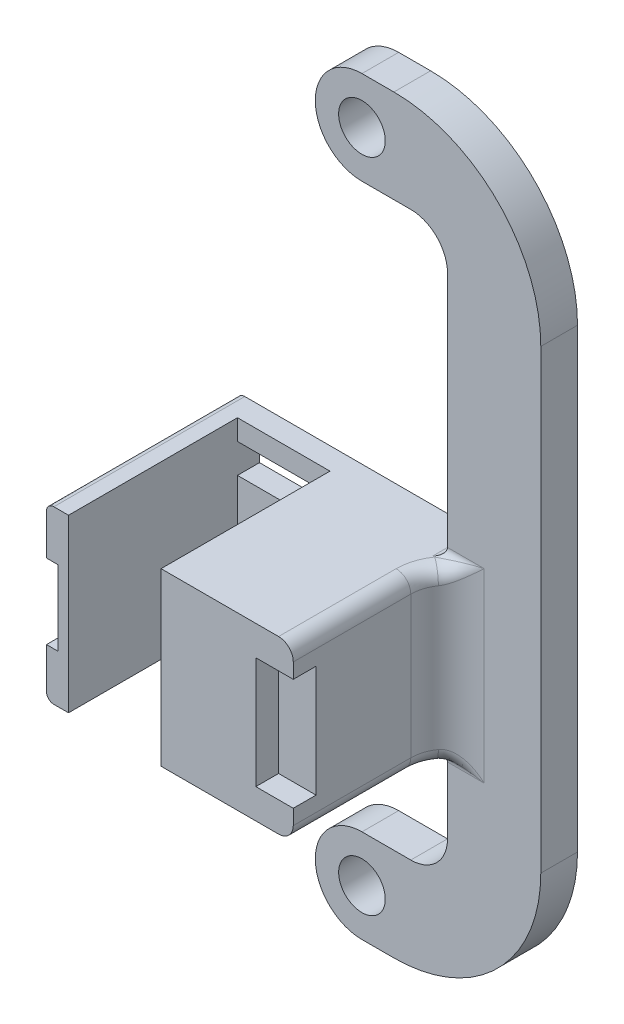
SolidWorks part; units mm, degrees
ref_plane "Front Plane" through (0, 0, 0) normal (0, 0, 1) x (1, 0, 0)
ref_plane "Top Plane" through (0, 0, 0) normal (0, 1, 0) x (1, 0, 0)
ref_plane "Right Plane" through (0, 0, 0) normal (1, 0, 0) x (0, 0, -1)
sketch "Sketch1" plane through (0, 0, 0) normal (0, 1, 0) x (1, 0, 0)
  line L1 (-6.3, -11.5) -> (6.3, -11.5)
  line L2 (-6.3, -11.5) -> (-6.3, 11.5)
  line L3 (-6.3, 11.5) -> (6.3, 11.5)
  line L4 (6.3, -11.5) -> (6.3, 11.5)
  line L5 (-6.3, -11.5) -> (6.3, 11.5) construction
  line L6 (-6.3, 11.5) -> (6.3, -11.5) construction
  point P0 (0, 0)
  dimension "D1" = 23
  dimension "D2" = 12.6
extrude "Extrude-Thin1" add sketch "Sketch1" along normal blind 23.3 thin thin type one direction wall 3
sketch "Sketch2" plane through (0, 0, 14.5) normal (0, 0, 1) x (1, 0, 0)
  line L0 (0, 23.3) -> (0, 0) construction
  line L1 (-9.3, 23.3) -> (9.3, 23.3) construction
  line L2 (-9.3, 0) -> (9.3, 0) construction
  line L4 (-6.3, 16.5) -> (6.3, 16.5)
  line L5 (-6.3, 16.5) -> (-6.3, 20.5)
  line L6 (-6.3, 20.5) -> (6.3, 20.5)
  line L7 (6.3, 16.5) -> (6.3, 20.5)
  line L8 (-6.3, 16.5) -> (6.3, 20.5) construction
  line L9 (-6.3, 20.5) -> (6.3, 16.5) construction
  point P6 (0, 18.5)
  dimension "D1" = 16.5
  dimension "D2" = 4
  dimension "D3" = 12.6
extrude "Cut-Extrude1" cut sketch "Sketch2" against normal through all
sketch "Sketch5" plane through (9.3, 0, 0) normal (1, 0, 0) x (0, 0, -1)
  line L1 (-14.5, 23.3) -> (14.5, 23.3)
  line L2 (-14.5, 23.3) -> (-14.5, 0)
  line L3 (-14.5, 0) -> (14.5, 0)
  line L4 (14.5, 23.3) -> (14.5, 0)
extrude "Boss-Extrude2" add sketch "Sketch5" along normal blind 15
sketch "Sketch6" plane through (0, 0, -14.5) normal (0, 0, -1) x (-1, 0, 0)
  line L0 (-24.3, 23.3) -> (9.3, 23.3) construction
  line L1 (-24.3, 68.004) -> (-37, 68.004)
  line L2 (-24.3, 68.004) -> (-24.3, -21.404)
  line L3 (-24.3, -21.404) -> (-37, -21.404)
  line L4 (-37, 68.004) -> (-37, -21.404)
  line L5 (-24.3, 0) -> (-24.3, 23.3) construction
  line L6 (-30.65, 68.004) -> (-12.65, 68.004)
  line L7 (-30.65, -15.054) -> (-12.65, -15.054)
  line L8 (-30.65, 71.179) -> (-12.65, 71.179)
  line L9 (-30.65, 71.179) -> (-30.65, 64.829)
  line L10 (-30.65, 64.829) -> (-12.65, 64.829)
  line L11 (-12.65, 71.179) -> (-12.65, 64.829)
  line L12 (-30.65, 74.354) -> (-12.65, 74.354)
  line L13 (-30.65, 74.354) -> (-30.65, 61.654)
  line L14 (-30.65, 61.654) -> (-12.65, 61.654)
  line L15 (-12.65, 74.354) -> (-12.65, 61.654)
  line L16 (-30.65, -27.754) -> (-12.65, -27.754)
  line L17 (-30.65, -27.754) -> (-37, -27.754)
  line L18 (-30.65, 61.654) -> (-37, 61.654)
  line L19 (-30.65, 61.654) -> (-30.65, 74.354)
  line L20 (-30.65, 74.354) -> (-37, 74.354)
  line L21 (-37, 61.654) -> (-37, 74.354)
  line L22 (-37, -15.054) -> (-37, -27.754)
  line L23 (-30.65, -15.054) -> (-37, -15.054)
  line L24 (-30.65, -15.054) -> (-30.65, -27.754)
  circle A0 centre (-30.65, 68.004) radius 3.175
  circle A1 centre (-30.65, -21.404) radius 3.175
  circle A2 centre (-30.65, 68.004) radius 6.35
  circle A3 centre (-30.65, -21.404) radius 6.35
  circle A4 centre (-12.65, 68.004) radius 3.175
  circle A5 centre (-12.65, 68.004) radius 6.35
  circle A6 centre (-12.65, -21.404) radius 3.175
  circle A7 centre (-12.65, -21.404) radius 6.35
  line M8 (-24.3, 23.3) -> (-24.3, 0)
  dimension "D3" = 6.35
  dimension "D4" = 6.35
  dimension "D5" = 12.7
  dimension "D1" = 89.408
  dimension "D2" = 44.704
  dimension "D6" = 0
  dimension "D7" = 18
extrude "Boss-Extrude3" add sketch "Sketch6" against normal blind 5 contours L23 L7 L2 L14 L18 L4 M8 | A2 L20 L21 | A2 L4 L18 | A2 L14 L2 L10 | A2 L10 L2 | A5 L8 A2 L6 | A5 L12 A2 L8 | A5 L6 L2 L10 | A5 L10 L2 L14 | L6 A5 L10 A4 | L8 A5 L6 A4 | L15 A5 L8 | L10 A5 L15 | L15 A5 A4 | A3 L23 L4 | L24 A3 L3 A1 | L3 A3 L24 A1 | A3 L2 L7 | L24 A3 L3 A1 | L3 A3 L24 A1 | A3 L22 L17 | L16 A7 L7 L2 A3 | A7 A6 | L3 A1 L24 | L24 A1 L3 | L3 A1 L24 | L24 A1 L3 | A2 region at (21.5066, 66.3767, -14.5) region at (21.65, 69.6673, -14.5) region at (24.552, 65.6117, -14.5) region at (20.3224, 63.0978, -14.5) region at (25.8496, 62.7868, -14.5) region at (16.8727, 69.6967, -14.5) region at (16.8727, 66.3113, -14.5) region at (21.65, 72.9849, -14.5) region at (30.65, 23.3, -14.5) region at (14.8039, 63.5271, -14.5) region at (14.8039, 72.4809, -14.5) region at (35.5816, 72.9356, -14.5) region at (35.5816, 63.0724, -14.5) region at (12.508, 63.2415, -14.5) region at (35.5816, -16.4724, -14.5) region at (21.2725, -21.8615, -14.5) region at (25.7184, -16.4724, -14.5) region at (33.7942, -18.2598, -14.5) region at (35.5816, -26.3356, -14.5) region at (33.7942, -24.5482, -14.5) region at (27.5058, -18.2598, -14.5) region at (27.5058, -24.5482, -14.5) region at (8.2869, -17.0409, -14.5) region at (31.9975, -20.0565, -14.5) region at (31.9975, -22.7515, -14.5) region at (29.3025, -20.0565, -14.5) region at (29.3025, -22.7515, -14.5)
fillet "Fillet1" radius 1 2 edges at (-9.3, 23.3, 0) (-9.3, 0, 0)
fillet "Fillet3" radius 5 1 edges at (24.3, 11.65, -9.5)
fillet "Fillet4" radius 1 4 edges at (24.3, 0, -12) (26.8, 0, -9.5) (26.8, 23.3, -9.5) (24.3, 23.3, -12)
fillet "Fillet5" radius 2 6 edges at (27.0916, 23.426, -8.9859) (24.8279, 23.3, -6.7361) (27.0916, -0.126, -8.9859) (24.8279, 0, -6.7361) (24.3, 23.3, 5) (24.3, 0, 5)
fillet "Fillet6" radius 5 2 edges at (24.3, -15.054, -12) (24.3, 61.654, -12)
fillet "Fillet7" radius 20 2 edges at (37, 74.354, -12) (37, -27.754, -12)
sketch "Sketch7" plane through (0, 0, 14.5) normal (0, 0, 1) x (1, 0, 0)
  line L0 (-9.3, 11.65) -> (24.3, 11.65) construction
  line L2 (-4.8, 6.65) -> (-7.8, 6.65)
  line L3 (-4.8, 6.65) -> (-4.8, 16.65)
  line L4 (6.3, 16.5) -> (-6.3, 16.5)
  line L5 (6.3, 0) -> (6.3, 16.5)
  line L6 (-6.3, 0) -> (6.3, 0)
  line L7 (-6.3, 16.5) -> (-6.3, 0)
  line L8 (6.3, 16.5) -> (-6.3, 16.5)
  line L9 (6.3, 0) -> (6.3, 16.5)
  line L10 (-6.3, 0) -> (6.3, 0)
  line L11 (-6.3, 16.5) -> (-6.3, 0)
  line L12 (-6.3, 20.5) -> (6.3, 20.5)
  line L13 (-6.3, 23.3) -> (-6.3, 20.5)
  line L14 (6.3, 23.3) -> (-6.3, 23.3)
  line L15 (6.3, 20.5) -> (6.3, 23.3)
  line L16 (-6.3, 20.5) -> (6.3, 20.5)
  line L17 (-6.3, 23.3) -> (-6.3, 20.5)
  line L18 (6.3, 23.3) -> (-6.3, 23.3)
  line L19 (6.3, 20.5) -> (6.3, 23.3)
  line L20 (24.3, 2) -> (24.3, 21.3)
  line L21 (22.3, 23.3) -> (-8.3, 23.3)
  line L22 (-9.3, 22.3) -> (-9.3, 1)
  line L23 (-8.3, 0) -> (22.3, 0)
  line L24 (24.3, 2) -> (24.3, 21.3)
  line L25 (22.3, 23.3) -> (-8.3, 23.3)
  line L26 (-9.3, 22.3) -> (-9.3, 1)
  line L27 (-8.3, 0) -> (22.3, 0)
  line L28 (-4.8, 16.65) -> (-7.8, 16.65)
  line L29 (-7.8, 6.65) -> (-7.8, 16.65)
  line L30 (-4.8, 6.65) -> (-7.8, 16.65) construction
  line L31 (-4.8, 16.65) -> (-7.8, 6.65) construction
  line L32 (19.3, 4.15) -> (29.3, 4.15)
  line L33 (19.3, 4.15) -> (19.3, 19.15)
  line L34 (19.3, 19.15) -> (29.3, 19.15)
  line L35 (29.3, 4.15) -> (29.3, 19.15)
  line L36 (19.3, 4.15) -> (29.3, 19.15) construction
  line L37 (19.3, 19.15) -> (29.3, 4.15) construction
  arc A4 (24.3, 21.3) -> (22.3, 23.3) centre (22.3, 21.3) ccw
  arc A5 (-8.3, 23.3) -> (-9.3, 22.3) centre (-8.3, 22.3) ccw
  arc A6 (-9.3, 1) -> (-8.3, 0) centre (-8.3, 1) ccw
  arc A7 (22.3, 0) -> (24.3, 2) centre (22.3, 2) ccw
  arc A8 (24.3, 21.3) -> (22.3, 23.3) centre (22.3, 21.3) ccw
  arc A9 (-8.3, 23.3) -> (-9.3, 22.3) centre (-8.3, 22.3) ccw
  arc A10 (-9.3, 1) -> (-8.3, 0) centre (-8.3, 1) ccw
  arc A11 (22.3, 0) -> (24.3, 2) centre (22.3, 2) ccw
  point P20 (-6.3, 11.65)
  point P21 (-6.3, 11.65)
  dimension "D4" = 10
  dimension "D5" = 3
  dimension "D6" = 10
  dimension "D7" = 15
  dimension "D1" = 0
  dimension "D2" = 0
  dimension "D3" = 0
sketch "Sketch8" plane through (-9.3, 0, 0) normal (-1, 0, 0) x (0, 0, 1)
  line L5 (-14.5, 74.354) -> (11.5, 74.354)
  line L6 (-14.5, 74.354) -> (-14.5, -28.4207)
  line L7 (-14.5, -28.4207) -> (11.5, -28.4207)
  line L8 (11.5, 74.354) -> (11.5, -28.4207)
  line L9 (11.5, 23.3) -> (14.5, 23.3)
  line L10 (11.5, 23.3) -> (11.5, 0)
  line L11 (11.5, 0) -> (14.5, 0)
  line L12 (14.5, 23.3) -> (14.5, 0)
  line L16 (-11.5, 23.3) -> (-11.5, 20.5)
  line L17 (-11.5, 20.5) -> (-14.5, 20.5)
  line L18 (-14.5, 20.5) -> (-14.5, 16.5)
  line L19 (-14.5, 16.5) -> (-11.5, 16.5)
  line L20 (-11.5, 16.5) -> (-11.5, 0)
  line L21 (-11.5, 0) -> (11.5, 0)
  line L22 (11.5, 0) -> (11.5, 16.5)
  line L23 (11.5, 16.5) -> (14.5, 16.5)
  line L24 (14.5, 16.5) -> (14.5, 20.5)
  line L25 (14.5, 20.5) -> (11.5, 20.5)
  line L26 (11.5, 20.5) -> (11.5, 23.3)
  line L27 (11.5, 23.3) -> (-11.5, 23.3)
  line L28 (-11.5, 23.3) -> (-11.5, 20.5)
  line L29 (-11.5, 20.5) -> (-14.5, 20.5)
  line L30 (-14.5, 20.5) -> (-14.5, 16.5)
  line L31 (-14.5, 16.5) -> (-11.5, 16.5)
  line L32 (-11.5, 16.5) -> (-11.5, 0)
  line L33 (-11.5, 0) -> (11.5, 0)
  line L34 (11.5, 0) -> (11.5, 16.5)
  line L35 (11.5, 16.5) -> (14.5, 16.5)
  line L36 (14.5, 16.5) -> (14.5, 20.5)
  line L37 (14.5, 20.5) -> (11.5, 20.5)
  line L38 (11.5, 20.5) -> (11.5, 23.3)
  line L39 (11.5, 23.3) -> (-11.5, 23.3)
  line M17 (14.5, 1) -> (14.5, 22.3)
  line M18 (14.5, 22.3) -> (-14.5, 22.3)
  line M20 (-14.5, 1) -> (14.5, 1)
  dimension "D1" = 0
extrude "Cut-Extrude3" cut sketch "Sketch8" against normal through all contours L12 L9 L8 M18 | L37 L8 M17 M18 | L12 L37 L10 L35 | L35 L10 M20 M17 | L12 L8 L11 M20 region at (-9.3, 22.8, 13) region at (-9.3, 21.4, 13) region at (-9.3, 18.5, 13) region at (-9.3, 8.75, 13) region at (-9.3, 0.5, 13)
sketch "Sketch10" plane through (0, 0, 11.5) normal (0, 0, 1) x (1, 0, 0)
  line L5 (-4.8, 16.65) -> (-7.8, 16.65) construction
  line L6 (-10.9, 6.55) -> (-7.7, 6.55)
  line L7 (29.4, 4.05) -> (19.2, 4.05)
  line L8 (29.4, 4.05) -> (29.4, 19.25)
  line L9 (29.4, 19.25) -> (19.2, 19.25)
  line L10 (19.2, 4.05) -> (19.2, 19.25)
  line L11 (29.4, 4.05) -> (19.2, 19.25) construction
  line L12 (29.4, 19.25) -> (19.2, 4.05) construction
  line L14 (19.3, 4.15) -> (19.3, 19.15) construction
  line L15 (19.3, 19.15) -> (29.3, 19.15) construction
  line L16 (-10.9, 6.55) -> (-10.9, 16.75)
  line L17 (-10.9, 16.75) -> (-7.7, 16.75)
  line L18 (-7.7, 6.55) -> (-7.7, 16.75)
  line L19 (-10.9, 6.55) -> (-7.7, 16.75) construction
  line L20 (-10.9, 16.75) -> (-7.7, 6.55) construction
  line L21 (-7.8, 6.65) -> (-7.8, 16.65) construction
  point P0 (-6.3, 11.65)
  point P1 (-9.3, 11.65)
  point P6 (24.3, 11.65)
  dimension "D1" = 0.1
  dimension "D2" = 0.1
  dimension "D3" = 0.1
  dimension "D4" = 0.1
extrude "Cut-Extrude4" cut sketch "Sketch10" against normal blind 3.1
